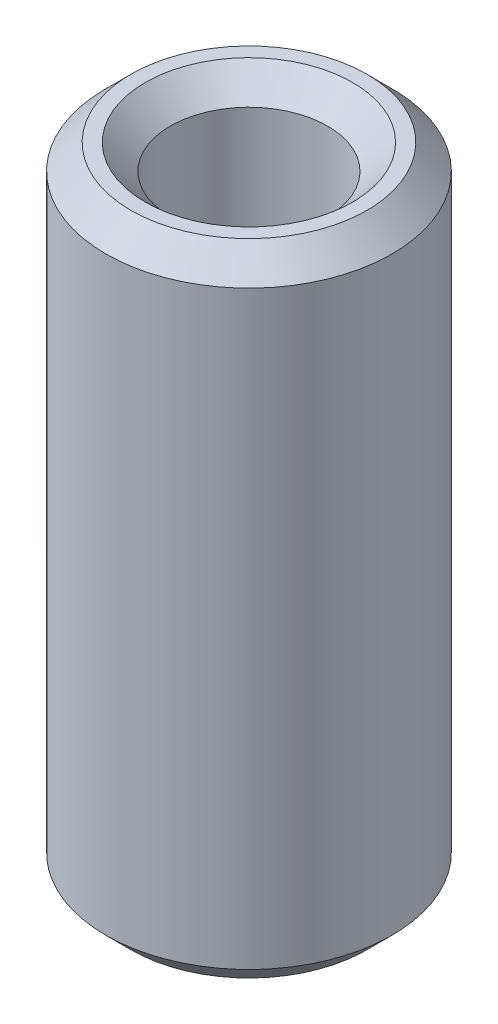
SolidWorks part; units mm, degrees
ref_plane "Front Plane" through (0, 0, 0) normal (0, 0, 1) x (1, 0, 0)
ref_plane "Top Plane" through (0, 0, 0) normal (0, 1, 0) x (1, 0, 0)
ref_plane "Right Plane" through (0, 0, 0) normal (1, 0, 0) x (0, 0, -1)
sketch "Sketch1" plane through (0, 0, 0) normal (0, 1, 0) x (1, 0, 0)
  circle A0 centre (0, 0) radius 22.5
  dimension "SLEEVE_OD" = 45
extrude "Boss-Extrude1" add sketch "Sketch1" along normal blind 100.6646
sketch "Sketch2" plane through (0, 0, 0) normal (0, 1, 0) x (1, 0, 0)
  circle A0 centre (0, 0) radius 12.3486
  dimension "BORE_D" = 24.6971
extrude "Cut-Extrude1" cut sketch "Sketch2" along normal through all
chamfer "Chamfer1" distance 3.9517 angle 45 4 edges at (0, 100.6646, 12.3486) (0, 0, 12.3486) (0, 0, 22.5) (0, 100.6646, 22.5)
